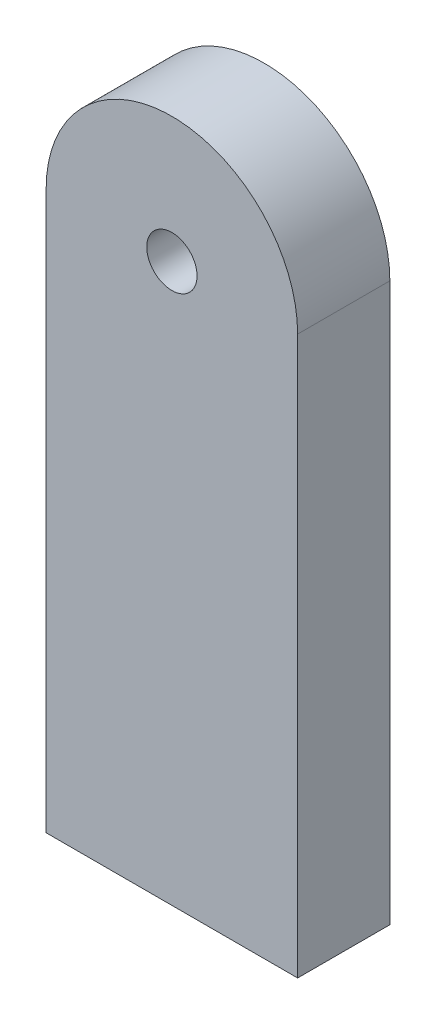
SolidWorks part; units mm, degrees
ref_plane "Front Plane" through (0, 0, 0) normal (0, 0, 1) x (1, 0, 0)
ref_plane "Top Plane" through (0, 0, 0) normal (0, 1, 0) x (1, 0, 0)
ref_plane "Right Plane" through (0, 0, 0) normal (1, 0, 0) x (0, 0, -1)
sketch "Sketch1" plane through (0, 0, 0) normal (0, 0, 1) x (1, 0, 0)
  line L0 (-3.3929, 0.0822) -> (3.3071, 0.0822)
  line L1 (-0.0429, -2.9178) -> (-0.0429, 3.0822)
  line L2 (-3.3929, -0.136) -> (-3.3929, 0.3005) construction
  line L3 (-2.4681, 0.0822) -> (-4.3177, 0.0822) construction
  line L4 (-1.9069, 2.8743) -> (-1.5289, 3.0926) construction
  line L5 (-1.2555, 2.1825) -> (-2.1803, 3.7843) construction
  line L6 (1.4431, 3.0926) -> (1.8211, 2.8743) construction
  line L7 (1.1697, 2.1825) -> (2.0945, 3.7843) construction
  line L8 (3.3071, 0.3005) -> (3.3071, -0.136) construction
  line L9 (2.3823, 0.0822) -> (4.2319, 0.0822) construction
  line L10 (1.8211, -2.7098) -> (1.4431, -2.9281) construction
  line L11 (1.1697, -2.018) -> (2.0945, -3.6198) construction
  line L12 (-1.5289, -2.9281) -> (-1.9069, -2.7098) construction
  line L13 (-1.2555, -2.018) -> (-2.1803, -3.6198) construction
  line L14 (-3.3929, 0.0822) -> (-1.7179, -2.8189)
  line L15 (-1.7179, -2.8189) -> (1.6321, -2.8189)
  line L16 (1.6321, -2.8189) -> (3.3071, 0.0822)
  line L17 (3.3071, 0.0822) -> (1.6321, 2.9834)
  line L18 (1.6321, 2.9834) -> (-1.7179, 2.9834)
  line L19 (-1.7179, 2.9834) -> (-3.3929, 0.0822)
  line L20 (7.4571, 0.0822) -> (7.4571, -33.1765)
  line L21 (7.4571, -33.1765) -> (-7.5429, -33.1765)
  line L22 (-7.5429, -33.1765) -> (-7.5429, 0.0822)
  circle A0 centre (-0.0429, 0.0822) radius 1.5
  circle A1 centre (-0.0429, 0.0822) radius 3.35 construction
  circle A2 centre (-0.0429, 0.0822) radius 7.5
  point P2 (-0.0429, 0.0822)
  point P5 (-0.0429, 0.0822)
  point P11 (-3.3929, 0.0822)
  point P14 (-3.3929, 0.0822)
  point P42 (0, 0)
  point P45 (0, 0)
  dimension "D1" = 6.7
  dimension "D3" = 15
  dimension "D2" = 5.8024
extrude "Boss-Extrude1" add sketch "Sketch1" along normal blind 2.5 contours A2 L19 L18 L17 L16 L15 L14 | A2 L22 L21 L20 region at (-0.0429, -7.2056, 0) region at (-0.0429, -19.4412, 0)
sketch "Sketch3" plane through (0, 0, 2.5) normal (0, 0, 1) x (1, 0, 0)
  line L0 (7.4571, 0.0822) -> (7.4571, -33.1765) construction
  line L1 (7.4571, -33.1765) -> (-7.5429, -33.1765) construction
  line L2 (-7.5429, -33.1765) -> (-7.5429, 0.0822) construction
  line L3 (7.4571, 0.0822) -> (7.4571, -33.1765)
  line L4 (7.4571, -33.1765) -> (-7.5429, -33.1765)
  line L5 (-7.5429, -33.1765) -> (-7.5429, 0.0822)
  arc A0 (7.4571, 0.0822) -> (-7.5429, 0.0822) centre (-0.0429, 0.0822) ccw construction
  arc A1 (7.4571, 0.0822) -> (-7.5429, 0.0822) centre (-0.0429, 0.0822) ccw
  circle A2 centre (-0.0429, 0.0822) radius 1.5
  dimension "D1" = 3
extrude "Boss-Extrude2" add sketch "Sketch3" along normal blind 3
